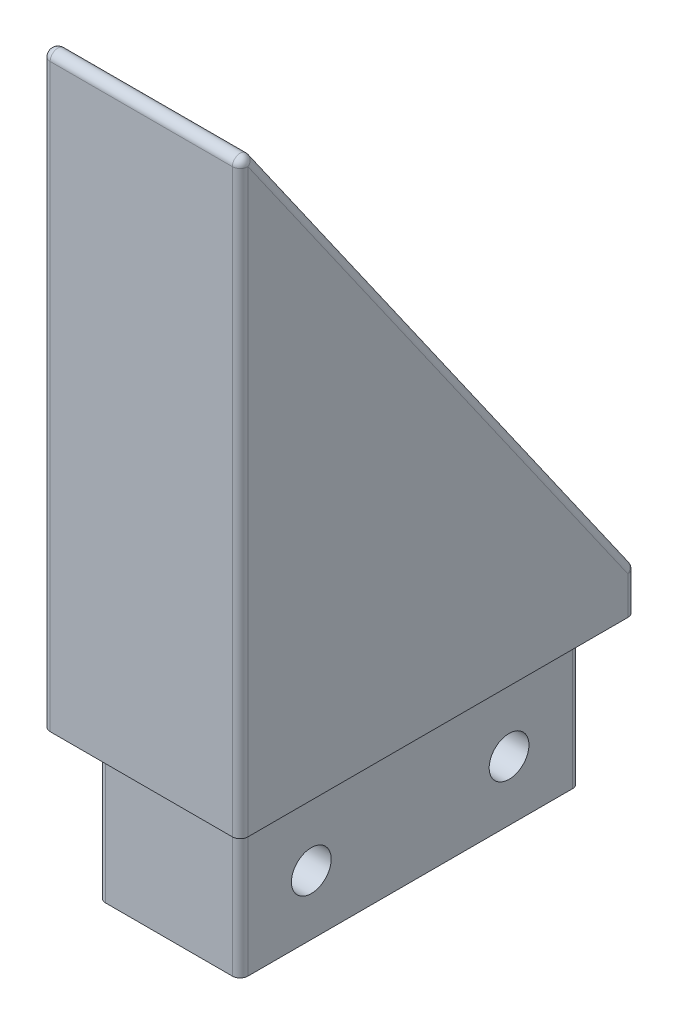
SolidWorks part; units mm, degrees
material "Nylon 101"
ref_plane "Front Plane" through (0, 0, 0) normal (0, 0, 1) x (1, 0, 0)
ref_plane "Top Plane" through (0, 0, 0) normal (0, 1, 0) x (1, 0, 0)
ref_plane "Right Plane" through (0, 0, 0) normal (1, 0, 0) x (0, 0, -1)
sketch "Sketch1" plane through (0, 0, 0) normal (1, 0, 0) x (0, 0, -1)
  line L0 (0, 0) -> (0, 77.724)
  line L1 (0, 77.724) -> (50.8, 5.1741)
  line L2 (50.8, 5.1741) -> (50.8, 0)
  line L3 (50.8, 0) -> (0, 0)
  dimension "D1" = 55
  dimension "D2" = 77.724
  dimension "D3" = 50.8
extrude "Boss-Extrude1" add sketch "Sketch1" along normal mid plane 25.4
sketch "Sketch2" plane through (0, 0, 0) normal (0, -1, 0) x (1, 0, 0)
  line L0 (0, -47.244) -> (0, -50.8) construction
  line L1 (9.144, -3.556) -> (-9.144, -3.556)
  line L2 (9.144, -3.556) -> (9.144, -47.244)
  line L3 (9.144, -47.244) -> (-9.144, -47.244)
  line L4 (-9.144, -3.556) -> (-9.144, -47.244)
  line L5 (12.7, -50.8) -> (-12.7, -50.8) construction
  line L6 (9.144, -25.4) -> (12.7, -25.4) construction
  line L7 (12.7, 0) -> (12.7, -50.8) construction
  dimension "D1" = 43.688
  dimension "D2" = 18.288
  dimension "D3" = 3.556
extrude "Boss-Extrude2" add sketch "Sketch2" along normal blind 19.05
fillet "Fillet1" radius 1 12 edges at (12.7, 41.449, -25.4) (-12.7, 41.449, -25.4) (9.144, -9.525, -3.556) (-9.144, -9.525, -47.244) (9.144, -9.525, -47.244) (-12.7, 38.862, 0) (12.7, 38.862, 0) (12.7, 2.587, -50.8) (-12.7, 2.587, -50.8) (-9.144, -9.525, -3.556) (0, 5.1741, -50.8) (0, 77.724, 0)
sketch "Sketch3" plane through (9.144, 0, 0) normal (1, 0, 0) x (0, 0, -1)
  line L0 (4.556, -11.3754) -> (46.244, -11.3754) construction
  line L1 (4.556, 0) -> (4.556, -19.05) construction
  line L2 (46.244, -19.05) -> (46.244, 0) construction
  line L3 (47.244, 0) -> (47.244, -19.05) construction
  circle A1 centre (38.1, -11.3754) radius 2.5527
  circle A2 centre (12.7, -11.3754) radius 2.5527
  point P6 (12.7, -11.3754)
  dimension "D2" = 9.144
  dimension "D4" = 5.1054
  dimension "D1" = 25.4
extrude "Cut-Extrude1" cut sketch "Sketch3" against normal through all
